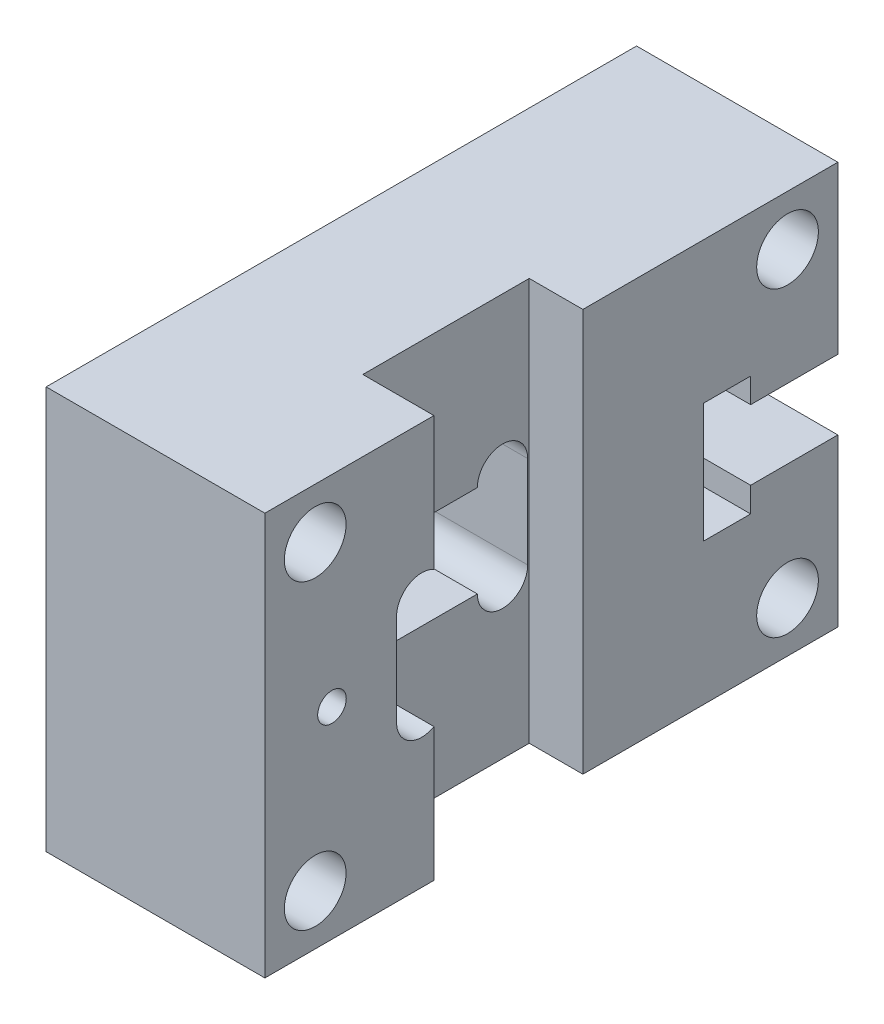
SolidWorks part; units mm, degrees
ref_plane "Front Plane" through (0, 0, 0) normal (1, 0, 0) x (0, 1, 0)
ref_plane "Top Plane" through (0, 0, 0) normal (0, 0, 1) x (0, 1, 0)
ref_plane "Right Plane" through (0, 0, 0) normal (0, 1, 0) x (-1, 0, 0)
sketch "Sketch1" plane through (0, 0, 0) normal (1, 0, 0) x (0, 1, 0)
  line L1 (-19.05, 25.4) -> (19.05, 25.4)
  line L2 (-19.05, 25.4) -> (-19.05, -25.4)
  line L3 (-19.05, -25.4) -> (19.05, -25.4)
  line L4 (19.05, 25.4) -> (19.05, -25.4)
  line L5 (-19.05, 25.4) -> (19.05, -25.4) construction
  line L6 (-19.05, -25.4) -> (19.05, 25.4) construction
  point P0 (0, 0)
  dimension "D1" = 38.1
  dimension "D2" = 50.8
extrude "Boss-Extrude1" add sketch "Sketch1" along normal blind 19.05
sketch "Sketch2" plane through (19.05, 0, 0) normal (1, 0, 0) x (0, 1, 0)
  line L0 (-19.05, 25.4) -> (-19.05, -25.4) construction
  line L1 (-19.05, 2.54) -> (19.05, 2.54)
  line L2 (-19.05, 2.54) -> (-19.05, -25.4)
  line L3 (-19.05, -25.4) -> (19.05, -25.4)
  line L4 (19.05, 2.54) -> (19.05, -25.4)
  dimension "D1" = 27.94
extrude "Boss-Extrude2" add sketch "Sketch2" along normal blind 25.4
sketch "Sketch3" plane through (0, 0, 0) normal (-1, 0, 0) x (0, -1, 0)
  line L0 (5.6515, -17.145) -> (3.302, -17.145) construction
  line L1 (-5.6515, -12.7) -> (5.6515, -12.7)
  line L2 (-5.6515, -12.7) -> (-5.6515, -17.145)
  line L3 (-5.6515, -17.145) -> (-3.302, -17.145)
  line L4 (5.6515, -12.7) -> (5.6515, -17.145)
  line L5 (5.6515, -12.7) -> (5.6515, -17.145) construction
  line L6 (19.05, -25.4) -> (-19.05, -25.4) construction
  line L8 (-3.302, -17.145) -> (-3.302, -25.4)
  line L9 (-3.302, -25.4) -> (3.302, -25.4)
  line L10 (3.302, -17.145) -> (3.302, -25.4)
  line L11 (3.302, -17.145) -> (3.302, -25.4) construction
  line L12 (3.302, -17.145) -> (5.6515, -17.145)
extrude "Cut-Extrude1" cut sketch "Sketch3" against normal up to vertex (44.45 mm away) up to point (44.45, -19.05, 2.54)
sketch "Sketch4" plane through (19.05, 0, 0) normal (1, 0, 0) x (0, 1, 0)
  line L0 (3.7907, 3.7698) -> (3.7907, 14.3332)
  line L1 (-3.81, 19.0902) -> (3.7907, 19.0902)
  line L5 (3.7907, 19.0902) -> (3.7907, 14.3332)
  line L7 (3.7907, 19.0902) -> (-3.81, 19.0902)
  line L8 (-3.81, 19.0902) -> (-3.81, 14.3139)
  line L9 (-3.81, 14.3139) -> (-3.81, 3.7698)
  line L10 (-3.81, 3.7698) -> (3.7907, 3.7698)
extrude "Cut-Extrude2" cut sketch "Sketch4" against normal up to surface (19.05 mm away) contours L9 L10 L0 L5 L1 L8 region at (19.05, -0.0097, 11.43) up to face at (0, 0, -12.065)
sketch "Sketch6" plane through (44.45, 0, 0) normal (1, 0, 0) x (0, 1, 0)
  line L0 (19.05, 2.54) -> (-19.05, 2.54) construction
  line L1 (-6.35, 2.54) -> (6.35, 2.54)
  line L2 (-6.35, 2.54) -> (-6.35, -6.985)
  line L3 (-6.35, -6.985) -> (6.35, -6.985)
  line L4 (6.35, 2.54) -> (6.35, -6.985)
  line L5 (0, 25.4) -> (0, -27.071) construction
  line L6 (19.05, 25.4) -> (-19.05, 25.4) construction
  point P11 (0, 2.54)
  dimension "D1" = 12.7
  dimension "D2" = 9.525
extrude "Cut-Extrude4" cut sketch "Sketch6" against normal up to surface (25.4 mm away) up to face at (19.05, -0.0097, 11.43)
sketch "Sketch7" plane through (0, 0, -6.985) normal (0, 0, 1) x (1, 0, 0)
  line L0 (44.45, 0) -> (19.05, 0) construction
  line L1 (44.45, -6.35) -> (44.45, 6.35) construction
  line L2 (19.05, 6.35) -> (19.05, -6.35) construction
  circle A0 centre (25.4, 0) radius 3.175
  dimension "D1" = 6.35
  dimension "D2" = 6.35
extrude "Cut-Extrude5" cut sketch "Sketch7" against normal blind 0.508
sketch "Sketch8" plane through (0, 0, -6.985) normal (0, 0, 1) x (1, 0, 0)
  line L4 (19.05, 6.35) -> (19.05, -6.35)
  line L5 (19.05, -6.35) -> (44.45, -6.35)
  line L6 (44.45, -6.35) -> (44.45, 6.35)
  line L7 (44.45, 6.35) -> (19.05, 6.35)
  line L8 (19.05, 6.35) -> (19.05, -6.35)
  line L9 (19.05, -6.35) -> (44.45, -6.35)
  line L10 (44.45, -6.35) -> (44.45, 6.35)
  line L11 (44.45, 6.35) -> (19.05, 6.35)
  circle A1 centre (25.4, 0) radius 3.175
  circle A2 centre (25.4, 0) radius 3.175
  dimension "D1" = 0
  dimension "D2" = 0
extrude "Boss-Extrude3" add sketch "Sketch8" along normal blind 1.27
sketch "Sketch9" plane through (0, -19.05, 0) normal (0, -1, 0) x (1, 0, 0)
  line L0 (41.275, 2.54) -> (41.275, -0.635) construction
  line L1 (44.45, 2.54) -> (19.05, 2.54) construction
  line L2 (41.275, -0.635) -> (44.45, -0.635) construction
  line L3 (44.45, 2.54) -> (44.45, -25.4) construction
  circle A0 centre (41.275, -0.635) radius 1.7145
  dimension "D3" = 3.429
  dimension "D1" = 3.175
  dimension "D2" = 3.175
extrude "Cut-Extrude6" cut sketch "Sketch9" against normal up to vertex (38.1 mm away) up to point (44.45, 19.05, 2.54)
sketch "Sketch10" plane through (44.45, 0, 0) normal (1, 0, 0) x (0, 1, 0)
  circle A0 centre (-14.2875, 25.7175) radius 1.7145
  circle A1 centre (14.2875, 25.7175) radius 1.7145
  circle A2 centre (14.2875, -20.6375) radius 1.7145
  circle A3 centre (-14.2875, -20.6375) radius 1.7145
  point P2 (14.2875, 25.7175)
  point P5 (-14.2875, 25.7175)
  point P8 (-14.2875, -20.6375)
  point P11 (14.2875, -20.6375)
extrude "Cut-Extrude7" cut sketch "Sketch10" against normal up to vertex (44.45 mm away) up to point (0, -19.05, 25.4)
sketch "Sketch11" plane through (44.45, 0, 0) normal (1, 0, 0) x (0, 1, 0)
  circle A0 centre (-14.2875, -20.6375) radius 2.921
  circle A1 centre (14.2875, -20.6375) radius 2.921
  circle A2 centre (14.2875, 25.7175) radius 2.921
  circle A3 centre (-14.2875, 25.7175) radius 2.921
  dimension "D1" = 5.842
  dimension "D2" = 5.842
  dimension "D3" = 5.842
  dimension "D4" = 5.842
extrude "Cut-Extrude8" cut sketch "Sketch11" against normal blind 35.814
sketch "Sketch20" plane through (0, 19.05, 0) normal (0, 1, 0) x (-1, 0, 0)
  line L0 (2.7638, 21.1725) -> (-7.3718, 21.1725) construction
sketch "Sketch22" plane through (19.05, 0, 0) normal (1, 0, 0) x (0, 1, 0)
  line L0 (-3.81, 3.7698) -> (3.7907, 3.7698) construction
  line L1 (3.7907, 19.0902) -> (2.8517, 19.0902)
  line L4 (2.8517, 19.0902) -> (2.8517, 4.7861)
  line L5 (3.7907, 19.0902) -> (3.7907, 3.7698)
  line L6 (-3.81, 19.0902) -> (-2.9131, 19.0902)
  line L8 (-3.81, 3.7698) -> (3.7907, 3.7698)
  line L9 (-2.9131, 19.0902) -> (-2.9131, 4.7861)
  line L10 (-2.9131, 4.7861) -> (2.8517, 4.7861)
  line L12 (-3.81, 3.7698) -> (3.7907, 3.7698)
  line L14 (-3.81, 19.0902) -> (-3.81, 3.7698)
  line M15 (-3.81, 3.7698) -> (-3.81, 19.0902)
  line M16 (-3.81, 19.0902) -> (3.7907, 19.0902)
  line M17 (3.7907, 19.0902) -> (3.7907, 3.7698)
  line M18 (3.7907, 3.7698) -> (-3.81, 3.7698)
extrude "Boss-Extrude4" add sketch "Sketch22" against normal up to surface (19.05 mm away) contours L10 L9 L4 M16 M15 M18 M17 region at (19.05, 3.6196, 11.43) up to face at (0, -14.2875, -22.352)
sketch "Sketch23" plane through (19.05, 0, 0) normal (1, 0, 0) x (0, 1, 0)
  line L4 (0.2928, 4.7861) -> (-0.2928, 4.7861)
  line L7 (-2.7, 5.132) -> (-1.7864, 5.132) construction
  circle A0 centre (0, 5.132) radius 0.25 construction
  arc A1 (-0.2928, 4.7861) -> (0.2928, 4.7861) centre (0, 5.132) ccw
  dimension "D1" = 0.2032
extrude "Cut-Extrude9" cut sketch "Sketch23" against normal up to vertex (19.05 mm away) up to point (0, 2.8517, 4.7861)
sketch "Sketch24" plane through (19.05, 0, 0) normal (1, 0, 0) x (0, 1, 0)
  line L0 (-2.9131, 4.7861) -> (-2.9131, 4.9288)
  line L1 (-2.9131, 19.0902) -> (-2.9131, 4.7861) construction
  line L2 (-2.9131, 4.9288) -> (-0.4051, 4.9288)
  line L3 (2.8517, 19.0902) -> (2.8517, 4.7861) construction
  line L4 (2.8517, 4.9288) -> (2.8517, 4.7861)
  line L5 (2.8517, 4.7861) -> (0.2928, 4.7861)
  line L6 (1.475, 5.132) -> (2.7, 5.132) construction
  line L7 (0.4051, 4.9288) -> (2.8517, 4.9288)
  line L8 (-0.2928, 4.7861) -> (-2.9131, 4.7861)
  arc A0 (-0.4051, 4.9288) -> (-0.2928, 4.7861) centre (0, 5.132) ccw
  arc A1 (0.2928, 4.7861) -> (0.4051, 4.9288) centre (0, 5.132) ccw
  dimension "D1" = 0.2032
extrude "Boss-Extrude5" add sketch "Sketch24" against normal up to surface (19.05 mm away) up to face at (0, -0.0205, 9.5362)
sketch "Sketch25" plane through (19.05, 0, 0) normal (1, 0, 0) x (0, 1, 0)
  line L0 (-2.7, 18.232) -> (2.3223, 18.232) construction
  line L1 (2.8517, 19.0902) -> (2.8517, 4.9288) construction
  line L2 (-2.9131, 19.0902) -> (2.8517, 19.0902)
  line L3 (-2.9131, 19.0902) -> (-2.9131, 18.4352)
  line L4 (-2.9131, 18.4352) -> (2.8517, 18.4352)
  line L5 (2.8517, 19.0902) -> (2.8517, 18.4352)
  dimension "D1" = 0.2032
extrude "Boss-Extrude6" add sketch "Sketch25" against normal up to surface (19.05 mm away) up to face at (0, -0.0205, 9.6076)
sketch "Sketch27" plane through (19.05, 0, 0) normal (1, 0, 0) x (0, 1, 0)
  line L1 (-2.9131, 19.0902) -> (2.8517, 19.0902)
  line L2 (-2.9131, 19.0902) -> (-2.9131, 18.4352)
  line L3 (-2.9131, 18.4352) -> (2.8517, 18.4352)
  line L4 (2.8517, 19.0902) -> (2.8517, 18.4352)
extrude "Cut-Extrude10" cut sketch "Sketch27" against normal blind 3.048
chamfer "Chamfer1" distance 1.016 angle 45 1 edges at (16.002, -0.0307, 18.4352)
sketch "Sketch29" plane through (19.05, 0, 0) normal (1, 0, 0) x (0, 1, 0)
  line L0 (2.8517, 19.0902) -> (2.8517, 4.9288) construction
  line L1 (-2.9131, 4.9288) -> (2.8517, 4.9288)
  line L2 (-2.9131, 4.9288) -> (-2.9131, 3.9288)
  line L3 (-2.9131, 3.9288) -> (2.8517, 3.9288)
  line L4 (2.8517, 4.9288) -> (2.8517, 3.9288)
  line L5 (-0.3875, 4.132) -> (1.9868, 4.132) construction
  dimension "D1" = 0.2032
extrude "Cut-Extrude11" cut sketch "Sketch29" against normal blind 0.762
sketch "Sketch31" plane through (0, -19.05, 0) normal (0, -1, 0) x (1, 0, 0)
  line L1 (44.45, -25.4) -> (19.05, -25.4)
  line L2 (44.45, -25.4) -> (44.45, 2.54)
  line L3 (44.45, 2.54) -> (19.05, 2.54)
  line L4 (19.05, -25.4) -> (19.05, 2.54)
extrude "Cut-Extrude12" cut sketch "Sketch31" against normal up to vertex (38.1 mm away) up to point (44.45, 19.05, 2.54)
sketch "Sketch33" plane through (19.05, 0, 0) normal (1, 0, 0) x (0, 1, 0)
  line L0 (-19.05, 25.4) -> (-19.05, -25.4) construction
  line L1 (-19.05, 14.478) -> (19.05, 14.478)
  line L2 (-19.05, 14.478) -> (-19.05, -1.27)
  line L3 (-19.05, -1.27) -> (19.05, -1.27)
  line L4 (19.05, 14.478) -> (19.05, -1.27)
  line L5 (19.05, -25.4) -> (19.05, 25.4) construction
  line L6 (19.05, 25.4) -> (17.1912, 25.4) construction
  line L7 (5.6515, -12.7) -> (-5.6515, -12.7) construction
  dimension "D1" = 10.922
  dimension "D2" = 11.43
extrude "Cut-Extrude13" cut sketch "Sketch33" against normal blind 2.54
sketch "Sketch35" plane through (0, -19.05, 0) normal (0, -1, 0) x (1, 0, 0)
  line L1 (19.05, 25.4) -> (17.527, 25.4)
  line L2 (19.05, 25.4) -> (19.05, 14.478)
  line L3 (19.05, 14.478) -> (17.527, 14.478)
  line L4 (17.527, 25.4) -> (17.527, 14.478)
  line L5 (17.4, 17.3239) -> (17.4, 21.0948) construction
  dimension "D1" = 0.254
extrude "Cut-Extrude14" cut sketch "Sketch35" against normal up to vertex (38.1 mm away) up to point (19.05, 19.05, 14.478)
sketch "Sketch36" plane through (0, 0, 25.4) normal (0, 0, 1) x (1, 0, 0)
  line L1 (0, 19.05) -> (17.527, 19.05)
  line L2 (0, 19.05) -> (0, -19.05)
  line L3 (0, -19.05) -> (17.527, -19.05)
  line L4 (17.527, 19.05) -> (17.527, -19.05)
extrude "Boss-Extrude7" add sketch "Sketch36" along normal blind 5.08
sketch "Sketch37" plane through (17.527, 0, 0) normal (1, 0, 0) x (0, 1, 0)
  line L0 (0, 30.48) -> (0, 2.5802) construction
  line L1 (-19.05, 30.48) -> (19.05, 30.48) construction
  line L3 (0, 22.1738) -> (2.794, 23.7869)
  line L4 (2.794, 23.7869) -> (2.794, 27.0131)
  line L5 (2.794, 27.0131) -> (0, 28.6262)
  line L6 (0, 28.6262) -> (-2.794, 27.0131)
  line L7 (-2.794, 27.0131) -> (-2.794, 23.7869)
  line L8 (-2.794, 23.7869) -> (0, 22.1738)
  circle A0 centre (0, 25.4) radius 2.794 construction
  dimension "D1" = 5.588
  dimension "D2" = 5.08
extrude "Cut-Extrude15" cut sketch "Sketch37" against normal blind 2.54
sketch "Sketch38" plane through (14.987, 0, 0) normal (1, 0, 0) x (0, 1, 0)
  line L0 (0, 28.6262) -> (0, 22.1738) construction
  circle A0 centre (0, 25.4) radius 1.651
  dimension "D1" = 3.302
extrude "Cut-Extrude16" cut sketch "Sketch38" against normal up to vertex (14.987 mm away) up to point (0, 19.05, 30.48)
sketch "Sketch39" plane through (16.51, 0, 0) normal (1, 0, 0) x (0, 1, 0)
  line L9 (2.8517, 4.9288) -> (0.4051, 4.9288)
  line L10 (-0.4051, 4.9288) -> (-2.9131, 4.9288)
  line L11 (-2.9131, 4.9288) -> (-2.9131, 14.478)
  line L12 (-2.9131, 14.478) -> (-19.05, 14.478)
  line L13 (-19.05, 14.478) -> (-19.05, -1.27)
  line L14 (-19.05, -1.27) -> (19.05, -1.27)
  line L15 (19.05, -1.27) -> (19.05, 14.478)
  line L16 (19.05, 14.478) -> (2.8517, 14.478)
  line L17 (2.8517, 14.478) -> (2.8517, 4.9288)
  line L18 (2.8517, 4.9288) -> (0.4051, 4.9288)
  line L19 (-0.4051, 4.9288) -> (-2.9131, 4.9288)
  line L20 (-2.9131, 4.9288) -> (-2.9131, 14.478)
  line L21 (-2.9131, 14.478) -> (-19.05, 14.478)
  line L22 (-19.05, 14.478) -> (-19.05, -1.27)
  line L23 (-19.05, -1.27) -> (19.05, -1.27)
  line L24 (19.05, -1.27) -> (19.05, 14.478)
  line L25 (19.05, 14.478) -> (2.8517, 14.478)
  line L26 (2.8517, 14.478) -> (2.8517, 4.9288)
  arc A1 (-0.4051, 4.9288) -> (0.4051, 4.9288) centre (0, 5.132) ccw
  arc A2 (-0.4051, 4.9288) -> (0.4051, 4.9288) centre (0, 5.132) ccw
  dimension "D1" = 0
extrude "Cut-Extrude17" cut sketch "Sketch39" against normal blind 2.54
fillet "Fillet1" radius 2.54 1 edges at (19.05, 0, -1.27)
sketch "Sketch40" plane through (0, 0, 0) normal (-1, 0, 0) x (0, -1, 0)
  line L1 (-2.8712, 26.8713) -> (-2.7098, 23.6491)
  line L2 (-2.7098, 23.6491) -> (0.1614, 22.1778)
  line L3 (0.1614, 22.1778) -> (2.8712, 23.9287)
  line L4 (2.8712, 23.9287) -> (2.7098, 27.1509)
  line L5 (2.7098, 27.1509) -> (-0.1614, 28.6222)
  line L6 (-0.1614, 28.6222) -> (-2.8712, 26.8713)
  circle A0 centre (0, 25.4) radius 2.794 construction
  dimension "D1" = 5.588
extrude "Cut-Extrude18" cut sketch "Sketch40" against normal blind 8.128
sketch "Sketch41" plane through (14.987, 0, 0) normal (1, 0, 0) x (0, 1, 0)
  line L6 (-2.794, 23.7869) -> (0, 22.1738)
  line L7 (0, 22.1738) -> (2.794, 23.7869)
  line L8 (2.794, 23.7869) -> (2.794, 27.0131)
  line L9 (2.794, 27.0131) -> (0, 28.6262)
  line L10 (0, 28.6262) -> (-2.794, 27.0131)
  line L11 (-2.794, 27.0131) -> (-2.794, 23.7869)
  line L12 (-2.794, 23.7869) -> (0, 22.1738)
  line L13 (0, 22.1738) -> (2.794, 23.7869)
  line L14 (2.794, 23.7869) -> (2.794, 27.0131)
  line L15 (2.794, 27.0131) -> (0, 28.6262)
  line L16 (0, 28.6262) -> (-2.794, 27.0131)
  line L17 (-2.794, 27.0131) -> (-2.794, 23.7869)
  circle A0 centre (0, 25.4) radius 1.651 construction
  circle A1 centre (0, 25.4) radius 1.651
  dimension "D1" = 0
extrude "Boss-Extrude8" add sketch "Sketch41" along normal up to surface (2.54 mm away) up to face at (17.527, 0, 25.4)
sketch "Sketch42" plane through (13.97, 0, 0) normal (1, 0, 0) x (0, 1, 0)
  line L1 (-4.36, 18.015) -> (4.36, 18.015)
  line L2 (-4.36, 18.015) -> (-4.36, -1.125)
  line L3 (-4.36, -1.125) -> (4.36, -1.125)
  line L4 (4.36, 18.015) -> (4.36, -1.125)
extrude "Cut-Extrude19" cut sketch "Sketch42" along normal up to vertex (3.557 mm away) and the other way up to vertex (13.97 mm away) up to point (17.527, -19.05, 14.478) other way up to point (0, -19.05, 30.48)
sketch "Sketch43" plane through (17.527, 0, 0) normal (1, 0, 0) x (0, 1, 0)
  line L1 (-2.9131, 18.015) -> (2.8517, 18.015)
  line L2 (-2.9131, 18.015) -> (-2.9131, 19.0902)
  line L3 (-2.9131, 19.0902) -> (2.8517, 19.0902)
  line L4 (2.8517, 18.015) -> (2.8517, 19.0902)
extrude "Boss-Extrude9" add sketch "Sketch43" against normal up to vertex (17.527 mm away) up to point (0, -19.05, 30.48)
sketch "Sketch44" plane through (13.97, 0, 0) normal (1, 0, 0) x (0, 1, 0)
  line L0 (4.5632, 18.2182) -> (4.5632, -1.3282)
  line L1 (-4.36, 18.015) -> (4.36, 18.015)
  line L2 (-4.36, 18.015) -> (-4.36, -1.125)
  line L3 (-4.36, -1.125) -> (4.36, -1.125)
  line L4 (4.36, 18.015) -> (4.36, -1.125)
  line L5 (-4.5632, -1.3282) -> (4.5632, -1.3282)
  line L6 (-4.5632, 18.2182) -> (-4.5632, -1.3282)
  line L7 (-4.5632, 18.2182) -> (4.5632, 18.2182)
  dimension "D1" = 0.2032
extrude "Cut-Extrude20" cut sketch "Sketch44" along normal up to vertex (3.557 mm away) and the other way up to vertex (13.97 mm away) up to point (17.527, 19.05, 30.48) other way up to point (0, 19.05, 30.48)
sketch "Sketch45" plane through (17.527, 0, 0) normal (1, 0, 0) x (0, 1, 0)
  line L8 (-4.5632, 14.478) -> (-4.5632, 18.2182)
  line L9 (-4.5632, 18.2182) -> (4.5632, 18.2182)
  line L10 (4.5632, 18.2182) -> (4.5632, 14.478)
  line L11 (4.5632, 14.478) -> (19.05, 14.478)
  line L12 (19.05, 14.478) -> (19.05, 30.48)
  line L13 (19.05, 30.48) -> (-19.05, 30.48)
  line L14 (-19.05, 30.48) -> (-19.05, 14.478)
  line L15 (-19.05, 14.478) -> (-4.5632, 14.478)
  line L16 (-4.5632, 14.478) -> (-4.5632, 18.2182)
  line L17 (-4.5632, 18.2182) -> (4.5632, 18.2182)
  line L18 (4.5632, 18.2182) -> (4.5632, 14.478)
  line L19 (4.5632, 14.478) -> (19.05, 14.478)
  line L20 (19.05, 14.478) -> (19.05, 30.48)
  line L21 (19.05, 30.48) -> (-19.05, 30.48)
  line L22 (-19.05, 30.48) -> (-19.05, 14.478)
  line L23 (-19.05, 14.478) -> (-4.5632, 14.478)
  circle A0 centre (-14.2875, 25.7175) radius 2.921 construction
  circle A1 centre (14.2875, 25.7175) radius 2.921 construction
  circle A2 centre (-14.2875, 25.7175) radius 2.921
  circle A3 centre (14.2875, 25.7175) radius 2.921
  circle A4 centre (0, 25.4) radius 1.651 construction
  circle A5 centre (0, 25.4) radius 1.651
  dimension "D1" = 0
extrude "Boss-Extrude10" add sketch "Sketch45" along normal blind 3.175
sketch "Sketch46" plane through (13.97, 0, 0) normal (1, 0, 0) x (0, 1, 0)
  line L1 (-4.5632, 18.2182) -> (4.5632, 18.2182)
  line L2 (-4.5632, 18.2182) -> (-4.5632, -1.3282)
  line L3 (-4.5632, -1.3282) -> (4.5632, -1.3282)
  line L4 (4.5632, 18.2182) -> (4.5632, -1.3282)
  line L5 (-4.36, 18.015) -> (4.36, 18.015)
  line L6 (-4.36, 18.015) -> (-4.36, -1.125)
  line L7 (-4.36, -1.125) -> (4.36, -1.125)
  line L8 (4.36, 18.015) -> (4.36, -1.125)
extrude "Boss-Extrude11" add sketch "Sketch46" against normal up to vertex (13.97 mm away) up to point (0, 19.05, 30.48)
sketch "Sketch47" plane through (13.97, 0, 0) normal (1, 0, 0) x (0, 1, 0)
  line L2 (4.36, -1.125) -> (4.36, 18.015) construction
  line L3 (-4.36, 18.015) -> (4.36, 18.015)
  line L4 (-4.36, 18.015) -> (-4.36, 14.478)
  line L6 (4.36, 18.015) -> (4.36, 14.478)
  line L7 (-4.36, 14.478) -> (-4.5632, 14.478)
  line L8 (4.36, 14.478) -> (4.5632, 14.478)
  line L9 (-4.5632, -1.27) -> (4.5632, -1.27)
  line L12 (19.05, 14.478) -> (4.5632, 14.478)
  line L13 (4.5632, 14.478) -> (4.5632, 18.2182)
  line L14 (4.5632, 18.2182) -> (-4.5632, 18.2182)
  line L15 (-4.5632, 18.2182) -> (-4.5632, 14.478)
  line L16 (-4.5632, 14.478) -> (-19.05, 14.478)
  line L17 (-19.05, 14.478) -> (-19.05, -1.27)
  line L18 (-19.05, -1.27) -> (-4.5632, -1.27)
  line L19 (-4.5632, -1.27) -> (-4.5632, -1.3282)
  line L20 (-4.5632, -1.3282) -> (4.5632, -1.3282)
  line L21 (4.5632, -1.3282) -> (4.5632, -1.27)
  line L22 (4.5632, -1.27) -> (19.05, -1.27)
  line L23 (19.05, -1.27) -> (19.05, 14.478)
  line L25 (4.5632, 14.478) -> (4.5632, 18.2182)
  line L26 (4.5632, 18.2182) -> (-4.5632, 18.2182)
  line L27 (-4.5632, 18.2182) -> (-4.5632, 14.478)
  line L31 (-4.5632, -1.27) -> (-4.5632, -1.3282)
  line L32 (-4.5632, -1.3282) -> (4.5632, -1.3282)
  line L33 (4.5632, -1.3282) -> (4.5632, -1.27)
  dimension "D1" = 0
extrude "Boss-Extrude12" add sketch "Sketch47" along normal up to vertex (6.732 mm away) up to point (20.702, -4.5632, 14.478)
sketch "Sketch48" plane through (0, -19.05, 0) normal (0, -1, 0) x (1, 0, 0)
  line L0 (19.05, -3.81) -> (19.05, -1.27)
  line L2 (16.51, -1.27) -> (19.05, -1.27)
  arc A0 (19.05, -3.81) -> (16.51, -1.27) centre (16.51, -3.81) ccw construction
  arc A1 (19.05, -3.81) -> (16.51, -1.27) centre (16.51, -3.81) ccw
extrude "Boss-Extrude13" add sketch "Sketch48" against normal up to vertex (38.1 mm away) up to point (19.05, 19.05, -3.81)
sketch "Sketch49" plane through (0, 0, -1.3282) normal (0, 0, -1) x (1, 0, 0)
  line L4 (20.702, 4.5632) -> (19.05, 4.5632)
  line L5 (19.05, 4.5632) -> (19.05, -4.5632)
  line L6 (19.05, -4.5632) -> (20.702, -4.5632)
  line L7 (20.702, -4.5632) -> (20.702, 4.5632)
  line L8 (20.702, 4.5632) -> (19.05, 4.5632)
  line L9 (19.05, 4.5632) -> (19.05, -4.5632)
  line L10 (19.05, -4.5632) -> (20.702, -4.5632)
  line L11 (20.702, -4.5632) -> (20.702, 4.5632)
  dimension "D1" = 0
extrude "Cut-Extrude21" cut sketch "Sketch49" against normal blind 0.762
sketch "Sketch50" plane through (20.702, 0, 0) normal (1, 0, 0) x (0, 1, 0)
  line L0 (4.36, 18.015) -> (15.8913, 18.015) construction
  line L5 (1.2696, -1.125) -> (13.1267, -1.125) construction
  line L6 (-4.36, -1.125) -> (4.36, -1.125) construction
  line L11 (-4.36, 14.478) -> (-4.36, 18.015) construction
  line L12 (4.36, 18.015) -> (4.36, 14.478) construction
  line L13 (-4.36, 14.478) -> (-4.36, -1.125) construction
  line L14 (4.36, -1.125) -> (4.36, 14.478) construction
  circle A4 centre (-4.36, 15.6337) radius 2.3813
  circle A5 centre (4.36, 15.6337) radius 2.3813
  circle A6 centre (-4.36, 1.2562) radius 2.3813
  circle A7 centre (4.36, 1.2562) radius 2.3813
  dimension "D1" = 4.7625
  dimension "D2" = 4.7625
  dimension "D3" = 4.7625
  dimension "D4" = 4.7625
extrude "Cut-Extrude22" cut sketch "Sketch50" against normal up to vertex (20.702 mm away) up to point (0, 19.05, 30.48)
sketch "Sketch51" plane through (8.636, 0, 0) normal (1, 0, 0) x (0, 1, 0)
  circle A0 centre (14.2875, 25.7175) radius 1.3525
  circle A1 centre (-14.2875, 25.7175) radius 1.3525
extrude "Cut-Extrude23" cut sketch "Sketch51" against normal blind 11.176 and the other way blind 15.494
sketch "Sketch52" plane through (17.527, 0, 0) normal (1, 0, 0) x (0, 1, 0)
  line L2 (-12.9727, 25.4) -> (-11.3838, 25.4)
  line L3 (-17.1912, 25.4) -> (-15.6023, 25.4)
  line L4 (-12.9727, 25.4) -> (-11.3838, 25.4)
  line L5 (-17.1912, 25.4) -> (-15.6023, 25.4)
  line L6 (15.6023, 25.4) -> (17.1912, 25.4)
  line L7 (11.3838, 25.4) -> (12.9727, 25.4)
  line L8 (15.6023, 25.4) -> (17.1912, 25.4)
  line L9 (11.3838, 25.4) -> (12.9727, 25.4)
  arc A2 (-12.9727, 25.4) -> (-15.6023, 25.4) centre (-14.2875, 25.7175) ccw
  arc A3 (-11.3838, 25.4) -> (-17.1912, 25.4) centre (-14.2875, 25.7175) ccw
  arc A4 (-12.9727, 25.4) -> (-15.6023, 25.4) centre (-14.2875, 25.7175) ccw
  arc A5 (-11.3838, 25.4) -> (-17.1912, 25.4) centre (-14.2875, 25.7175) ccw
  arc A6 (15.6023, 25.4) -> (12.9727, 25.4) centre (14.2875, 25.7175) ccw
  arc A7 (17.1912, 25.4) -> (11.3838, 25.4) centre (14.2875, 25.7175) ccw
  arc A8 (15.6023, 25.4) -> (12.9727, 25.4) centre (14.2875, 25.7175) ccw
  arc A9 (17.1912, 25.4) -> (11.3838, 25.4) centre (14.2875, 25.7175) ccw
  dimension "D1" = 0
  dimension "D2" = 0
extrude "Cut-Extrude24" cut sketch "Sketch52" against normal up to vertex (8.891 mm away) up to point (8.636, -11.3838, 25.4)
sketch "Sketch53" plane through (8.636, 0, 0) normal (1, 0, 0) x (0, 1, 0)
  circle A0 centre (-14.2875, 25.7175) radius 1.7145
  circle A1 centre (14.2875, 25.7175) radius 1.7145
extrude "Cut-Extrude25" cut sketch "Sketch53" against normal up to vertex (8.636 mm away) contours A1 | A0 up to point (0, 15.9723, 25.4)
sketch "Sketch54" plane through (0, 0, 0) normal (-1, 0, 0) x (0, -1, 0)
  line L6 (-0.1614, 28.6222) -> (-2.8712, 26.8713)
  line L7 (-2.8712, 26.8713) -> (-2.7098, 23.6491)
  line L8 (-2.7098, 23.6491) -> (0.1614, 22.1778)
  line L9 (0.1614, 22.1778) -> (2.8712, 23.9287)
  line L10 (2.8712, 23.9287) -> (2.7098, 27.1509)
  line L11 (2.7098, 27.1509) -> (-0.1614, 28.6222)
  line L12 (-0.1614, 28.6222) -> (-2.8712, 26.8713)
  line L13 (-2.8712, 26.8713) -> (-2.7098, 23.6491)
  line L14 (-2.7098, 23.6491) -> (0.1614, 22.1778)
  line L15 (0.1614, 22.1778) -> (2.8712, 23.9287)
  line L16 (2.8712, 23.9287) -> (2.7098, 27.1509)
  line L17 (2.7098, 27.1509) -> (-0.1614, 28.6222)
  dimension "D1" = 0
extrude "Boss-Extrude14" add sketch "Sketch54" against normal up to vertex (20.702 mm away) up to point (20.702, 19.05, 30.48)
sketch "Sketch55" plane through (20.702, 0, 0) normal (1, 0, 0) x (0, 1, 0)
  line L0 (0, 30.48) -> (0, -26.4021) construction
  line L1 (19.05, 30.48) -> (-19.05, 30.48) construction
sketch "Sketch56" plane through (8.636, 0, 0) normal (1, 0, 0) x (0, 1, 0)
  circle A0 centre (-14.2875, -20.6375) radius 2.921 construction
  circle A1 centre (14.2875, -20.6375) radius 2.921 construction
  circle A2 centre (14.2875, 25.7175) radius 2.921 construction
  circle A3 centre (-14.2875, 25.7175) radius 2.921 construction
  circle A4 centre (-14.2875, -20.6375) radius 2.921
  circle A5 centre (14.2875, -20.6375) radius 2.921
  circle A6 centre (14.2875, 25.7175) radius 2.921
  circle A7 centre (-14.2875, 25.7175) radius 2.921
  circle A8 centre (-14.2875, -20.6375) radius 1.7145 construction
  circle A9 centre (14.2875, -20.6375) radius 1.7145 construction
  circle A10 centre (14.2875, 25.7175) radius 1.7145 construction
  circle A11 centre (-14.2875, 25.7175) radius 1.7145 construction
  circle A12 centre (-14.2875, -20.6375) radius 1.7145
  circle A13 centre (14.2875, -20.6375) radius 1.7145
  circle A14 centre (14.2875, 25.7175) radius 1.7145
  circle A15 centre (-14.2875, 25.7175) radius 1.7145
extrude "Boss-Extrude15" add sketch "Sketch56" along normal blind 5.334
hole_wizard "#6-32 Tapped Hole1" positions "Sketch58" profile "Sketch59" tap size "#6-32" standard "ANSI Inch" end condition up to next
sketch "Sketch58" plane through (20.702, 0, 0) normal (1, 0, 0) x (0, 1, 0)
  line L0 (0, 30.48) -> (0, -26.4021) construction
  point P0 (0, 24.13)
  dimension "D1" = 6.35
sketch "Sketch59" plane through (20.702, 0, 24.13) normal (0, 1, 0) x (0, 0, -1)
  line L0 (0, 0) -> (0, 20.702)
  line L1 (0, 20.702) -> (1.3525, 20.702)
  line L2 (1.3525, 20.702) -> (1.3525, 0)
  line L5 (1.3525, 0) -> (0, 0)
  line L11 (0, -6.35) -> (0, 107.95) construction
  dimension "Thru Tap Drill Dia." = 2.7051
  dimension "Thru Tap Drill Depth" = 20.702
cosmetic thread "Hole Thread1" parameters "D2"=3.5052
